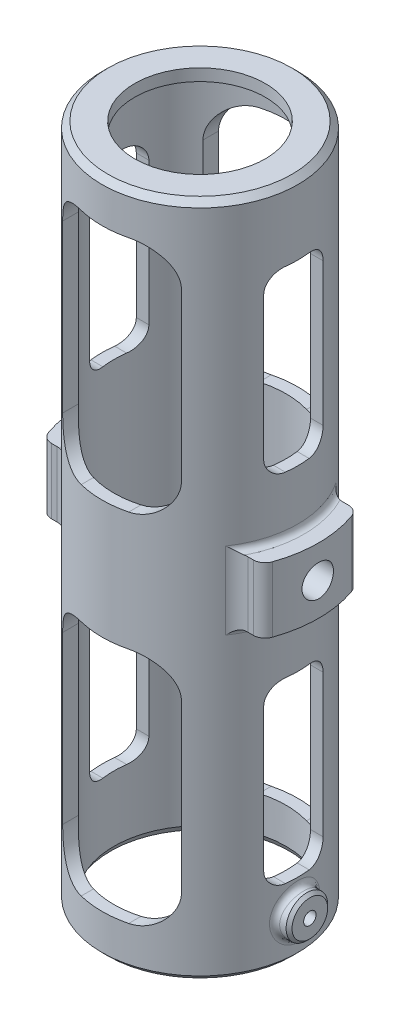
SolidWorks part; units mm, degrees
material "PLA"
ref_plane "Plan de face" through (0, 0, 0) normal (0, 0, 1) x (1, 0, 0)
ref_plane "Plan de dessus" through (0, 0, 0) normal (0, 1, 0) x (1, 0, 0)
ref_plane "Plan de droite" through (0, 0, 0) normal (1, 0, 0) x (0, 0, -1)
sketch "Esquisse1" plane through (0, 0, 0) normal (0, 1, 0) x (1, 0, 0)
  circle A0 centre (0, 0) radius 16.5
  circle A1 centre (0, 0) radius 14.5
  dimension "D1" = 33
  dimension "D2" = 29
extrude "Boss.-Extru.1" add sketch "Esquisse1" along normal mid plane 114
sketch "Esquisse11" plane through (0, 0, 0) normal (0, 1, 0) x (1, 0, 0)
  line L0 (14.4309, 8) -> (18.3303, 8)
  line L1 (20, 0) -> (20, -17.5) construction
  line L2 (18.3303, -8) -> (14.4309, -8)
  arc A0 (14.4309, -8) -> (14.4309, 8) centre (0, 0) ccw
  circle A1 centre (0, 0) radius 16.5 construction
  arc A2 (18.3303, -8) -> (18.3303, 8) centre (0, 0) ccw
  dimension "D1" = 20
  dimension "D2" = 8
extrude "Boss.-Extru.4" add sketch "Esquisse11" along normal mid plane 11
ref_plane "Plan1" through (16.5, 0, 0) normal (1, 0, 0) x (0, 0, -1)
ref_plane "Plan3" through (20, 0, 0) normal (1, 0, 0) x (0, 0, -1)
sketch "Esquisse3" plane through (20, 0, 0) normal (1, 0, 0) x (0, 0, -1)
  circle A0 centre (0, 0) radius 2.65
  dimension "D1" = 5.3
extrude "Enlèv. mat.-Extru.1" cut sketch "Esquisse3" against normal blind 4
mirror "Symétrie1" about plane through (0, 0, 0) normal (1, 0, 0) of "Boss.-Extru.4", "Enlèv. mat.-Extru.1"
sketch "Esquisse4" plane through (16.5, 0, 0) normal (1, 0, 0) x (0, 0, -1)
  circle A0 centre (0, -50) radius 3.5
  dimension "D1" = 7
  dimension "D2" = 50
extrude "Boss.-Extru.2" add sketch "Esquisse4" along normal blind 2 and the other way blind 1
sketch "Esquisse5" plane through (18.5, 0, 0) normal (1, 0, 0) x (0, 0, -1)
  circle A0 centre (0, -50) radius 1.05
  dimension "D1" = 2.1
extrude "Enlèv. mat.-Extru.2" cut sketch "Esquisse5" against normal up to next
sketch "Esquisse6" plane through (18.5, 0, 0) normal (1, 0, 0) x (0, 0, -1)
  circle A0 centre (0, -50) radius 2.5
  dimension "D1" = 5
extrude "Enlèv. mat.-Extru.3" cut sketch "Esquisse6" against normal blind 1.5 from offset 3 offset against normal yes
fillet "Congé1" radius 1 1 edges at (16.1405, -49.2819, 3.4255)
chamfer "Chanfrein1" distance 0.5 angle 45 1 edges at (18.5, -50, -3.5)
sketch "Esquisse7" plane through (0, 57, 0) normal (0, 1, 0) x (1, 0, 0)
  circle A0 centre (0, 0) radius 16.5
  circle A1 centre (0, 0) radius 16.5 construction
  circle A2 centre (0, 0) radius 11
  dimension "D1" = 22
extrude "Boss.-Extru.3" add sketch "Esquisse7" against normal blind 2
chamfer "Chanfrein2" distance 1 angle 45 1 edges at (0, 57, 16.5)
chamfer "Chanfrein5" distance 1 angle 45 1 edges at (0, -57, 16.5)
chamfer "Chanfrein3" distance 1 angle 30 1 edges at (0, -57, 14.5) first distance on face at (0, -57, 14.5)
sketch "Esquisse8" plane through (0, 0, 0) normal (0, 0, 1) x (1, 0, 0)
  line L1 (10, 50) -> (-10, 50) construction
  line L2 (10, 50) -> (10, -50) construction
  line L3 (10, -50) -> (-10, -50) construction
  line L4 (-10, 50) -> (-10, -50) construction
  line L5 (10, 50) -> (-10, -50) construction
  line L6 (10, -50) -> (-10, 50) construction
  line L7 (-10, 50) -> (10, 50)
  line L8 (-10, 50) -> (-10, 10)
  line L9 (-10, 10) -> (10, 10)
  line L10 (10, 50) -> (10, 10)
  line L11 (-10, -50) -> (10, -50)
  line L12 (-10, -50) -> (-10, -10)
  line L13 (-10, -10) -> (10, -10)
  line L14 (10, -50) -> (10, -10)
  point P0 (0, 0)
  dimension "D1" = 20
  dimension "D2" = 100
  dimension "D3" = 10
  dimension "D4" = 10
extrude "Enlèv. mat.-Extru.4" cut sketch "Esquisse8" against normal mid plane 50
sketch "Esquisse9" plane through (0, 0, 0) normal (1, 0, 0) x (0, 0, -1)
  line L0 (0, 0) -> (0, 30) construction
  line L1 (-13.1244, 30) -> (0, 30) construction
  line L3 (-13.1244, 50) -> (-13.1244, 10) construction
  line L4 (5, 45) -> (-5, 45)
  line L5 (5, 45) -> (5, 15)
  line L6 (5, 15) -> (-5, 15)
  line L7 (-5, 45) -> (-5, 15)
  line L8 (5, 45) -> (-5, 15) construction
  line L9 (5, 15) -> (-5, 45) construction
  dimension "D1" = 10
  dimension "D2" = 30
extrude "Enlèv. mat.-Extru.5" cut sketch "Esquisse9" against normal mid plane 40
fillet "Congé2" radius 6 16 edges at (-10, -50, 11.8122) (-10, -10, 11.8122) (10, -10, 11.8122) (10, -50, 11.8122) (-10, -50, -11.8122) (10, -50, -11.8122) (-10, -10, -11.8122) (10, -10, -11.8122) (-10, 10, -11.8122) (-10, 50, -11.8122) (10, 50, -11.8122) (10, 10, -11.8122) (10, 10, 11.8122) (-10, 10, 11.8122) (10, 50, 11.8122) (-10, 50, 11.8122)
fillet "Congé3" radius 3 8 edges at (14.6674, 15, 5) (14.6674, 15, -5) (14.6674, 45, -5) (14.6674, 45, 5) (-14.6674, 15, -5) (-14.6674, 15, 5) (-14.6674, 45, 5) (-14.6674, 45, -5)
mirror "Symétrie2" about plane through (0, 0, 0) normal (0, 1, 0) of "Congé3", "Enlèv. mat.-Extru.5"
fillet "Congé6" radius 2 4 edges at (18.3303, 0, 8) (-18.3303, 0, 8) (18.3303, 0, -8) (-18.3303, 0, -8)
fillet "Congé7" radius 3 4 edges at (14.4309, 0, -8) (14.4309, 0, 8) (-14.4309, 0, 8) (-14.4309, 0, -8)
fillet "Congé8" radius 1 4 edges at (-16.5, -5.5, 0) (-16.5, 5.5, 0) (16.5, -5.5, 0) (16.5, 5.5, 0)
